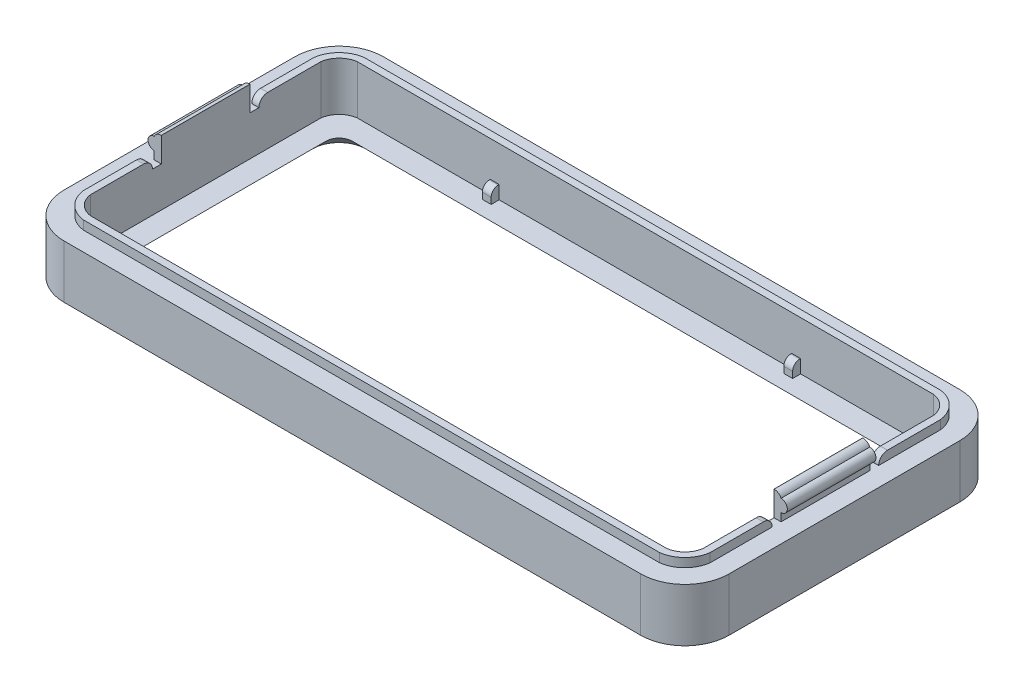
SolidWorks part; units mm, degrees
ref_plane "前视基准面" through (0, 0, 0) normal (0, 0, 1) x (1, 0, 0)
ref_plane "上视基准面" through (0, 0, 0) normal (0, 1, 0) x (1, 0, 0)
ref_plane "右视基准面" through (0, 0, 0) normal (1, 0, 0) x (0, 0, -1)
sketch "zero" plane through (0, 0, 0) normal (0, 1, 0) x (1, 0, 0)
  line L1 (-29.5, 15) -> (29.5, 15)
  line L2 (-32.5, 12) -> (-32.5, -12)
  line L3 (-29.5, -15) -> (29.5, -15)
  line L4 (32.5, 12) -> (32.5, -12)
  line L5 (-32.5, 15) -> (32.5, -15) construction
  line L6 (-32.5, -15) -> (32.5, 15) construction
  line L7 (-25.7, -15) -> (-14.5, -15)
  line L8 (-25.7, -15) -> (-25.7, -9.6569)
  line L9 (-25.7, -9.6569) -> (-14.5, -9.6569)
  line L10 (-14.5, -15) -> (-14.5, -9.6569)
  line L11 (5.2, -15) -> (12.7, -15)
  line L12 (5.2, -15) -> (5.2, -11)
  line L13 (5.2, -11) -> (12.7, -11)
  line L14 (12.7, -15) -> (12.7, -11)
  line L15 (17.8, -15) -> (25.3, -15)
  line L16 (17.8, -15) -> (17.8, -11)
  line L17 (17.8, -11) -> (25.3, -11)
  line L18 (25.3, -15) -> (25.3, -11)
  line L19 (-32.5, 7.7) -> (-19.5, 7.7)
  line L20 (-32.5, 7.7) -> (-32.5, -4.3)
  line L21 (-32.5, -4.3) -> (-19.5, -4.3)
  line L22 (-19.5, 7.7) -> (-19.5, -4.3)
  line L23 (-25.5, 14) -> (25.5, 14)
  line L24 (-25.5, 14) -> (-25.5, 8.8)
  line L25 (-25.5, 8.8) -> (25.5, 8.8)
  line L26 (25.5, 14) -> (25.5, 8.8)
  line L27 (-19.5, 7.2329) -> (-35.5, 7.2329)
  line L28 (-19.5, 7.2329) -> (-19.5, -3.7671)
  line L29 (-19.5, -3.7671) -> (-35.5, -3.7671)
  line L30 (-35.5, 7.2329) -> (-35.5, -3.7671)
  arc A0 (29.5, -15) -> (32.5, -12) centre (29.5, -12) ccw
  arc A1 (29.5, 15) -> (32.5, 12) centre (29.5, 12) cw
  arc A2 (-32.5, -12) -> (-29.5, -15) centre (-29.5, -12) ccw
  arc A3 (-29.5, 15) -> (-32.5, 12) centre (-29.5, 12) ccw
  circle A4 centre (-29, 11.4) radius 3
  circle A5 centre (-29, -11.5) radius 3
  circle A6 centre (29, 11.4) radius 3
  circle A7 centre (29, -11.5) radius 3
  circle A8 centre (-29, 11.4) radius 1.375
  circle A9 centre (-29, -11.5) radius 1.375
  circle A10 centre (29, -11.5) radius 1.375
  circle A11 centre (29, 11.4) radius 1.375
  point P0 (0, 0)
  dimension "D3" = 3
  dimension "D4" = 6
  dimension "D9" = 2.75
  dimension "D1" = 65
  dimension "D2" = 30
  dimension "D5" = 3.6
  dimension "D6" = 3.5
  dimension "D7" = 3.5
  dimension "D8" = 3.5
  dimension "D10" = 12
  dimension "D11" = 7.3
  dimension "D12" = 13
  dimension "D13" = 11.2
  dimension "D14" = 6.8
  dimension "D15" = 19.7
  dimension "D16" = 7.5
  dimension "D17" = 7.5
  dimension "D18" = 5.1
  dimension "D19" = 4
  dimension "D20" = 5.2
  dimension "D21" = 7
  dimension "D22" = 7
  dimension "D23" = 1
  dimension "D24" = 11
  dimension "D25" = 16
sketch "sugar" plane through (0, 0, 0) normal (0, 1, 0) x (1, 0, 0)
  line L1 (-29.5, 15) -> (29.5, 15)
  line L2 (-32.5, 12) -> (-32.5, -12)
  line L3 (-29.5, -15) -> (29.5, -15)
  line L4 (32.5, 12) -> (32.5, -12)
  line L5 (-32.5, 15) -> (32.5, -15) construction
  line L6 (-32.5, -15) -> (32.5, 15) construction
  line L7 (23.5, -11.5) -> (19.5, -11.5)
  line L8 (23.5, -11.5) -> (23.5, -13.9082)
  line L9 (23.5, -13.9082) -> (19.5, -13.9082)
  line L10 (19.5, -11.5) -> (19.5, -13.9082)
  line L11 (16, -11.0071) -> (8.5, -11.0071)
  line L12 (16, -11.0071) -> (16, -15)
  line L13 (16, -15) -> (8.5, -15)
  line L14 (8.5, -11.0071) -> (8.5, -15)
  line L15 (20.5, -13.9082) -> (22.5, -13.9082)
  line L16 (20.5, -13.9082) -> (20.5, -14.8173)
  line L17 (20.5, -14.8173) -> (22.5, -14.8173)
  line L18 (22.5, -13.9082) -> (22.5, -14.8173)
  arc A0 (29.5, 15) -> (32.5, 12) centre (29.5, 12) cw
  arc A1 (29.5, -15) -> (32.5, -12) centre (29.5, -12) ccw
  arc A2 (-32.5, -12) -> (-29.5, -15) centre (-29.5, -12) ccw
  arc A3 (-29.5, 15) -> (-32.5, 12) centre (-29.5, 12) ccw
  circle A4 centre (-29, 11.4) radius 3
  circle A5 centre (-29, 11.4) radius 1.375
  circle A6 centre (-29, -11.5) radius 3
  circle A7 centre (-29, -11.5) radius 1.375
  circle A8 centre (29, 11.4) radius 3
  circle A9 centre (29, 11.4) radius 1.375
  circle A10 centre (29, -11.5) radius 3
  circle A11 centre (29, -11.5) radius 1.375
  dimension "D3" = 3
  dimension "D1" = 65
  dimension "D2" = 30
  dimension "D4" = 9
  dimension "D5" = 4
  dimension "D6" = 3.5
  dimension "D7" = 7.5
  dimension "D8" = 2
  dimension "D9" = 1
sketch "case" plane through (0, 0, 0) normal (0, 1, 0) x (1, 0, 0)
  line L1 (-34.0422, 18) -> (30.9578, 18)
  line L2 (-39.0422, 13) -> (-39.0422, -13)
  line L3 (-34.0422, -18) -> (30.9578, -18)
  line L4 (35.9578, 13) -> (35.9578, -13)
  line L5 (-39.0422, 18) -> (35.9578, -18) construction
  line L6 (-39.0422, -18) -> (35.9578, 18) construction
  arc A0 (-39.0422, -13) -> (-34.0422, -18) centre (-34.0422, -13) ccw
  arc A1 (30.9578, -18) -> (35.9578, -13) centre (30.9578, -13) ccw
  arc A2 (30.9578, 18) -> (35.9578, 13) centre (30.9578, 13) cw
  arc A3 (-34.0422, 18) -> (-39.0422, 13) centre (-34.0422, 13) ccw
  point P0 (-1.5422, 0)
  point P3 (-1.5422, 0)
  dimension "D3" = 5
  dimension "D1" = 75
  dimension "D2" = 36
extrude "凸台-拉伸2" add sketch "case" along normal blind 6
sketch "草图2" plane through (0, 0, 0) normal (0, 1, 0) x (1, 0, 0)
  line L4 (-34.0422, -15.05) -> (30.9578, -15.05)
  line L5 (33.0078, -13) -> (33.0078, 13)
  line L6 (30.9578, 15.05) -> (-34.0422, 15.05)
  line L7 (-36.0922, 13) -> (-36.0922, -13)
  line L12 (33.8078, -13) -> (33.8078, 13)
  line L13 (30.9578, 15.85) -> (-34.0422, 15.85)
  line L14 (-36.8922, 13) -> (-36.8922, -13)
  line L15 (-34.0422, -15.85) -> (30.9578, -15.85)
  arc A4 (30.9578, -15.05) -> (33.0078, -13) centre (30.6303, -12.6725) ccw
  arc A5 (33.0078, 13) -> (30.9578, 15.05) centre (30.6303, 12.6725) ccw
  arc A6 (-34.0422, 15.05) -> (-36.0922, 13) centre (-33.7147, 12.6725) ccw
  arc A7 (-36.0922, -13) -> (-34.0422, -15.05) centre (-33.7147, -12.6725) ccw
  arc A12 (30.9578, -15.85) -> (33.8078, -13) centre (30.535, -12.5772) ccw
  arc A13 (33.8078, 13) -> (30.9578, 15.85) centre (30.535, 12.5772) ccw
  arc A14 (-34.0422, 15.85) -> (-36.8922, 13) centre (-33.6194, 12.5772) ccw
  arc A15 (-36.8922, -13) -> (-34.0422, -15.85) centre (-33.6194, -12.5772) ccw
ref_plane "基准面1" through (0, 6, 0) normal (0, 1, 0) x (1, 0, 0)
sketch "草图3" plane through (0, 6, 0) normal (0, 1, 0) x (1, 0, 0)
  line L4 (-34.0422, -15.05) -> (30.9578, -15.05)
  line L5 (33.0078, -13) -> (33.0078, 13)
  line L6 (30.9578, 15.05) -> (-34.0422, 15.05)
  line L7 (-36.0922, 13) -> (-36.0922, -13)
  line L8 (-34.0422, -15.05) -> (30.9578, -15.05)
  line L9 (33.0078, -13) -> (33.0078, 13)
  line L10 (30.9578, 15.05) -> (-34.0422, 15.05)
  line L11 (-36.0922, 13) -> (-36.0922, -13)
  line L12 (-36.8922, 13) -> (-36.8922, -13)
  line L13 (-34.0422, -15.85) -> (30.9578, -15.85)
  line L14 (33.8078, -13) -> (33.8078, 13)
  line L15 (30.9578, 15.85) -> (-34.0422, 15.85)
  line L16 (-36.8922, 13) -> (-36.8922, -13)
  line L17 (-34.0422, -15.85) -> (30.9578, -15.85)
  line L18 (33.8078, -13) -> (33.8078, 13)
  line L19 (30.9578, 15.85) -> (-34.0422, 15.85)
  arc A4 (30.9578, -15.05) -> (33.0078, -13) centre (30.6303, -12.6725) ccw
  arc A5 (33.0078, 13) -> (30.9578, 15.05) centre (30.6303, 12.6725) ccw
  arc A6 (-34.0422, 15.05) -> (-36.0922, 13) centre (-33.7147, 12.6725) ccw
  arc A7 (-36.0922, -13) -> (-34.0422, -15.05) centre (-33.7147, -12.6725) ccw
  arc A8 (30.9578, -15.05) -> (33.0078, -13) centre (30.6303, -12.6725) ccw
  arc A9 (33.0078, 13) -> (30.9578, 15.05) centre (30.6303, 12.6725) ccw
  arc A10 (-34.0422, 15.05) -> (-36.0922, 13) centre (-33.7147, 12.6725) ccw
  arc A11 (-36.0922, -13) -> (-34.0422, -15.05) centre (-33.7147, -12.6725) ccw
  arc A12 (-36.8922, -13) -> (-34.0422, -15.85) centre (-33.6194, -12.5772) ccw
  arc A13 (30.9578, -15.85) -> (33.8078, -13) centre (30.535, -12.5772) ccw
  arc A14 (33.8078, 13) -> (30.9578, 15.85) centre (30.535, 12.5772) ccw
  arc A15 (-34.0422, 15.85) -> (-36.8922, 13) centre (-33.6194, 12.5772) ccw
  arc A16 (-36.8922, -13) -> (-34.0422, -15.85) centre (-33.6194, -12.5772) ccw
  arc A17 (30.9578, -15.85) -> (33.8078, -13) centre (30.535, -12.5772) ccw
  arc A18 (33.8078, 13) -> (30.9578, 15.85) centre (30.535, 12.5772) ccw
  arc A19 (-34.0422, 15.85) -> (-36.8922, 13) centre (-33.6194, 12.5772) ccw
  dimension "D1" = 0
  dimension "D2" = 0
extrude "凸台-拉伸4" add sketch "草图3" along normal blind 1
ref_plane "基准面3" through (33.8078, 0, 0) normal (1, 0, 0) x (0, 0, -1)
sketch "草图7" plane through (0, 6, 0) normal (0, 1, 0) x (1, 0, 0)
  line L0 (-36.8922, 13) -> (-36.8922, -13) construction
  line L1 (-36.8922, 5) -> (-36.0922, 5)
  line L2 (-36.8922, 5) -> (-36.8922, -5)
  line L3 (-36.8922, -5) -> (-36.0922, -5)
  line L4 (-36.0922, 5) -> (-36.0922, -5)
  line L5 (-36.0922, 13) -> (-36.0922, -13) construction
  point P10 (-36.0922, 0)
  dimension "D1" = 5
  dimension "D2" = 10
extrude "凸台-拉伸8" add sketch "草图7" along normal blind 2.8
ref_plane "基准面5" through (0, 0, 5) normal (0, 0, 1) x (1, 0, 0)
sketch "草图8" plane through (0, 0, 5) normal (0, 0, 1) x (1, 0, 0)
  line L0 (-34.0422, 6) -> (-39.0422, 6) construction
  line L1 (-36.8922, 8.8) -> (-36.8922, 7) construction
  circle A0 centre (-36.8922, 7.6) radius 0.7
  dimension "D1" = 1.4
  dimension "D2" = 1.6
  dimension "D3" = 0
extrude "凸台-拉伸9" add sketch "草图8" against normal blind 10
fillet "圆角1" radius 0.85 1 edges at (-36.8922, 8.8, 0)
ref_plane "基准面7" through (-36.8922, 0, 0) normal (-1, 0, 0) x (0, 0, 1)
sketch "草图11" plane through (-36.8922, 0, 0) normal (-1, 0, 0) x (0, 0, 1)
  line L0 (-13, 6) -> (13, 6) construction
  line L1 (5, 7) -> (6, 7)
  line L2 (5, 7) -> (5, 6)
  line L3 (5, 6) -> (6, 6)
  line L4 (6, 7) -> (6, 6)
  line L6 (-5, 7) -> (-6, 7)
  line L7 (-5, 7) -> (-5, 6)
  line L8 (-5, 6) -> (-6, 6)
  line L9 (-6, 7) -> (-6, 6)
  dimension "D1" = 1
  dimension "D2" = 1
extrude "切除-拉伸1" cut sketch "草图11" against normal blind 1.2
fillet "圆角2" radius 1 2 edges at (-36.4922, 7, 6) (-36.4922, 7, -6)
ref_plane "基准面8" through (0, 0, 0) normal (0, -1, 0) x (-1, 0, 0)
sketch "草图13" plane through (0, 7, 0) normal (0, 1, 0) x (1, 0, 0)
  line L0 (33.0078, -13) -> (33.0078, 13) construction
  line L1 (33.0078, 5) -> (33.8078, 5)
  line L2 (33.0078, 5) -> (33.0078, -5)
  line L3 (33.0078, -5) -> (33.8078, -5)
  line L4 (33.8078, 5) -> (33.8078, -5)
  line L5 (33.8078, -13) -> (33.8078, 13) construction
  line L7 (35.9578, -13) -> (35.9578, 13) construction
  point P12 (35.9578, 0)
  point P13 (33.8078, 0)
  dimension "D1" = 10
extrude "凸台-拉伸10" add sketch "草图13" along normal blind 1.8
sketch "草图14" plane through (0, 0, 5) normal (0, 0, 1) x (1, 0, 0)
  line L0 (33.8078, 6) -> (30.9578, 6) construction
  line L1 (33.8078, 8.8) -> (33.8078, 7) construction
  circle A0 centre (33.8078, 7.6) radius 0.7
  dimension "D2" = 1.4
  dimension "D1" = 1.6
  dimension "D3" = 0
extrude "凸台-拉伸11" add sketch "草图14" against normal blind 10
fillet "圆角3" radius 0.85 1 edges at (33.8078, 8.8, 0)
sketch "草图15" plane through (0, 7, 0) normal (0, 1, 0) x (1, 0, 0)
  line L0 (33.8078, 5) -> (33.8078, 13) construction
  line L1 (33.0078, 5) -> (33.8078, 5)
  line L2 (33.0078, 5) -> (33.0078, 6)
  line L3 (33.0078, 6) -> (33.8078, 6)
  line L4 (33.8078, 5) -> (33.8078, 6)
  line L5 (33.8078, -13) -> (33.8078, -5) construction
  line L6 (33.0078, -5) -> (33.8078, -5)
  line L7 (33.0078, -5) -> (33.0078, -6)
  line L8 (33.0078, -6) -> (33.8078, -6)
  line L9 (33.8078, -5) -> (33.8078, -6)
  dimension "D1" = 1
  dimension "D2" = 1
extrude "切除-拉伸3" cut sketch "草图15" against normal blind 1
fillet "圆角4" radius 1 2 edges at (33.4078, 7, 6) (33.4078, 7, -6)
sketch "草图16" plane through (0, 6, 0) normal (0, 1, 0) x (1, 0, 0)
  line L4 (-34.0422, -15.05) -> (30.9578, -15.05)
  line L5 (33.0078, -13) -> (33.0078, 13)
  line L6 (30.9578, 15.05) -> (-34.0422, 15.05)
  line L7 (-36.0922, 13) -> (-36.0922, -13)
  line L8 (-34.0422, -15.05) -> (30.9578, -15.05)
  line L9 (33.0078, -13) -> (33.0078, 13)
  line L10 (30.9578, 15.05) -> (-34.0422, 15.05)
  line L11 (-36.0922, 13) -> (-36.0922, -13)
  arc A4 (30.9578, -15.05) -> (33.0078, -13) centre (30.6303, -12.6725) ccw
  arc A5 (33.0078, 13) -> (30.9578, 15.05) centre (30.6303, 12.6725) ccw
  arc A6 (-34.0422, 15.05) -> (-36.0922, 13) centre (-33.7147, 12.6725) ccw
  arc A7 (-36.0922, -13) -> (-34.0422, -15.05) centre (-33.7147, -12.6725) ccw
  arc A8 (30.9578, -15.05) -> (33.0078, -13) centre (30.6303, -12.6725) ccw
  arc A9 (33.0078, 13) -> (30.9578, 15.05) centre (30.6303, 12.6725) ccw
  arc A10 (-34.0422, 15.05) -> (-36.0922, 13) centre (-33.7147, 12.6725) ccw
  arc A11 (-36.0922, -13) -> (-34.0422, -15.05) centre (-33.7147, -12.6725) ccw
  dimension "D1" = 0
extrude "切除-拉伸4" cut sketch "草图16" against normal blind 4.5
sketch "草图17" plane through (0, 1.5, 0) normal (0, 1, 0) x (1, 0, 0)
  line L0 (30.9578, 18) -> (-34.0422, 18) construction
  line L1 (-33.5422, 12.5) -> (30.4578, 12.5)
  line L2 (-33.5422, 12.5) -> (-33.5422, -12.5)
  line L3 (-33.5422, -12.5) -> (30.4578, -12.5)
  line L4 (30.4578, 12.5) -> (30.4578, -12.5)
  line L5 (-39.0422, 13) -> (-39.0422, -13) construction
  point P4 (-1.5422, 12.5)
  point P7 (-1.5422, 18)
  point P8 (-33.5422, 0)
  point P11 (-39.0422, 0)
  dimension "D1" = 25
  dimension "D2" = 64
extrude "切除-拉伸5" cut sketch "草图17" against normal blind 1.5
fillet "圆角5" radius 1.5 4 edges at (30.4578, 0.75, 12.5) (30.4578, 0.75, -12.5) (-33.5422, 0.75, -12.5) (-33.5422, 0.75, 12.5)
sketch "草图20" plane through (0, 1.5, 0) normal (0, 1, 0) x (1, 0, 0)
  line L0 (30.9578, 15.05) -> (-34.0422, 15.05) construction
  line L1 (-19.0422, 15.05) -> (-18.0422, 15.05)
  line L2 (-19.0422, 15.05) -> (-19.0422, 14.15)
  line L3 (-19.0422, 14.15) -> (-18.0422, 14.15)
  line L4 (-18.0422, 15.05) -> (-18.0422, 14.15)
  line L6 (-34.0422, -15.05) -> (30.9578, -15.05) construction
  line L7 (15.9578, 15.05) -> (14.9578, 15.05)
  line L8 (15.9578, 15.05) -> (15.9578, 14.15)
  line L9 (15.9578, 14.15) -> (14.9578, 14.15)
  line L10 (14.9578, 15.05) -> (14.9578, 14.15)
  line L11 (-19.0422, -15.05) -> (-18.0422, -15.05)
  line L12 (-19.0422, -15.05) -> (-19.0422, -14.15)
  line L13 (-19.0422, -14.15) -> (-18.0422, -14.15)
  line L14 (-18.0422, -15.05) -> (-18.0422, -14.15)
  line L15 (-39.0422, 13) -> (-39.0422, -13) construction
  line L16 (14.9578, -15.05) -> (15.9578, -15.05)
  line L17 (14.9578, -15.05) -> (14.9578, -14.15)
  line L18 (14.9578, -14.15) -> (15.9578, -14.15)
  line L19 (15.9578, -15.05) -> (15.9578, -14.15)
  line L21 (35.9578, -13) -> (35.9578, 13) construction
  dimension "D1" = 20
  dimension "D2" = 20
  dimension "D3" = 1
  dimension "D4" = 1
  dimension "D5" = 20
  dimension "D6" = 20
  dimension "D7" = 1
  dimension "D8" = 1
  dimension "D9" = 0.9
  dimension "D10" = 0.9
  dimension "D11" = 0.9
  dimension "D12" = 0.9
extrude "凸台-拉伸14" add sketch "草图20" along normal blind 1.5
fillet "圆角8" radius 0.8 4 edges at (15.4578, 3, 14.15) (-18.5422, 3, 14.15) (15.4578, 3, -14.15) (-18.5422, 3, -14.15)
chamfer "倒角3" distance 1.5 angle 45 8 edges at (-1.5422, 0, -12.5) (-33.1029, 0, -12.0607) (30.0185, 0, -12.0607) (-33.5422, 0, 0) (30.4578, 0, 0) (-33.1029, 0, 12.0607) (30.0185, 0, 12.0607) (-1.5422, 0, 12.5)
